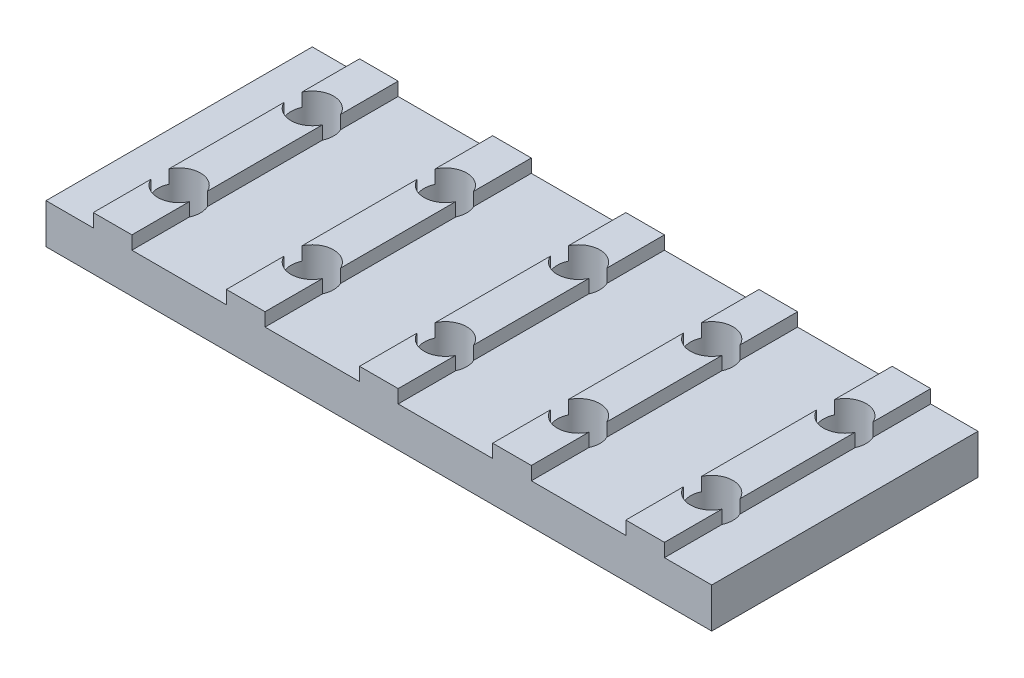
SolidWorks part; units mm, degrees
ref_plane "Front Plane" through (0, 0, 0) normal (0, 0, 1) x (1, 0, 0)
ref_plane "Top Plane" through (0, 0, 0) normal (0, 1, 0) x (1, 0, 0)
ref_plane "Right Plane" through (0, 0, 0) normal (1, 0, 0) x (0, 0, -1)
sketch "Esquisse1" plane through (0, 0, 0) normal (0, 0, 1) x (1, 0, 0)
  line L0 (-5, 0) -> (-5, 3)
  line L1 (-5, 3) -> (-1.45, 3)
  line L2 (-1.45, 3) -> (-1.45, 4)
  line L3 (-1.45, 4) -> (1.45, 4)
  line L4 (1.45, 4) -> (1.45, 3)
  line L5 (1.45, 3) -> (5, 3)
  line L6 (5, 3) -> (5, 0)
  line L7 (5, 0) -> (-5, 0)
  point P11 (0, 0)
  dimension "D1" = 10
  dimension "D2" = 3
  dimension "D3" = 1
  dimension "D4" = 2.9
  dimension "D5" = 3.55
extrude "Main" add sketch "Esquisse1" along normal blind 20
sketch "Esquisse2" plane through (0, 4, 0) normal (0, 1, 0) x (1, 0, 0)
  line L0 (0, -2.2) -> (0, 2.2) construction
  line L1 (-1.45, 0) -> (-5, 0) construction
  line L2 (-1.45, -20) -> (-5, -20) construction
  circle A0 centre (0, -5) radius 1.6
  circle A1 centre (0, -15) radius 1.6
  dimension "D2" = 5
  dimension "D3" = 3.2
  dimension "D1" = 5
extrude "TopHole" cut sketch "Esquisse2" against normal through all
ref_axis "Axe1" through (-5.5, 0, 0) along (1, 0, 0)
pattern_linear "Répétition linéaire1" count 5 spacing 10 along (-1, 0, 0) of "TopHole", "Main"
